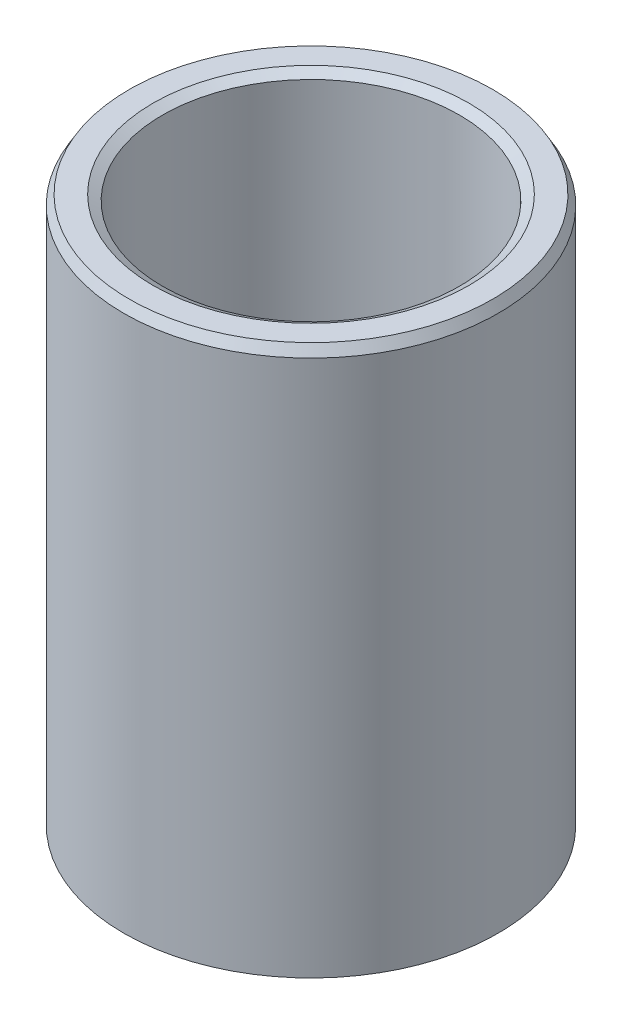
SolidWorks part; units mm, degrees
ref_plane "Front Plane" through (0, 0, 0) normal (0, 0, 1) x (1, 0, 0)
ref_plane "Top Plane" through (0, 0, 0) normal (0, 1, 0) x (1, 0, 0)
ref_plane "Right Plane" through (0, 0, 0) normal (1, 0, 0) x (0, 0, -1)
sketch "Sketch1" plane through (0, 0, 0) normal (0, 1, 0) x (1, 0, 0)
  circle A0 centre (0, 0) radius 27.5
  dimension "SLEEVE_OD" = 55
extrude "Boss-Extrude1" add sketch "Sketch1" along normal blind 81.067
sketch "Sketch2" plane through (0, 0, 0) normal (0, 1, 0) x (1, 0, 0)
  circle A0 centre (0, 0) radius 21.8016
  dimension "BORE_D" = 43.6032
extrude "Cut-Extrude1" cut sketch "Sketch2" along normal through all
chamfer "Chamfer1" distance 1.4007 angle 30 4 edges at (0, 81.067, 21.8016) (0, 0, 21.8016) (0, 0, 27.5) (0, 81.067, 27.5) first distance on face at (0, 81.067, 21.8016) first distance on face at (0, 0, 21.8016) first distance on face at (0, 81.067, 27.5)
